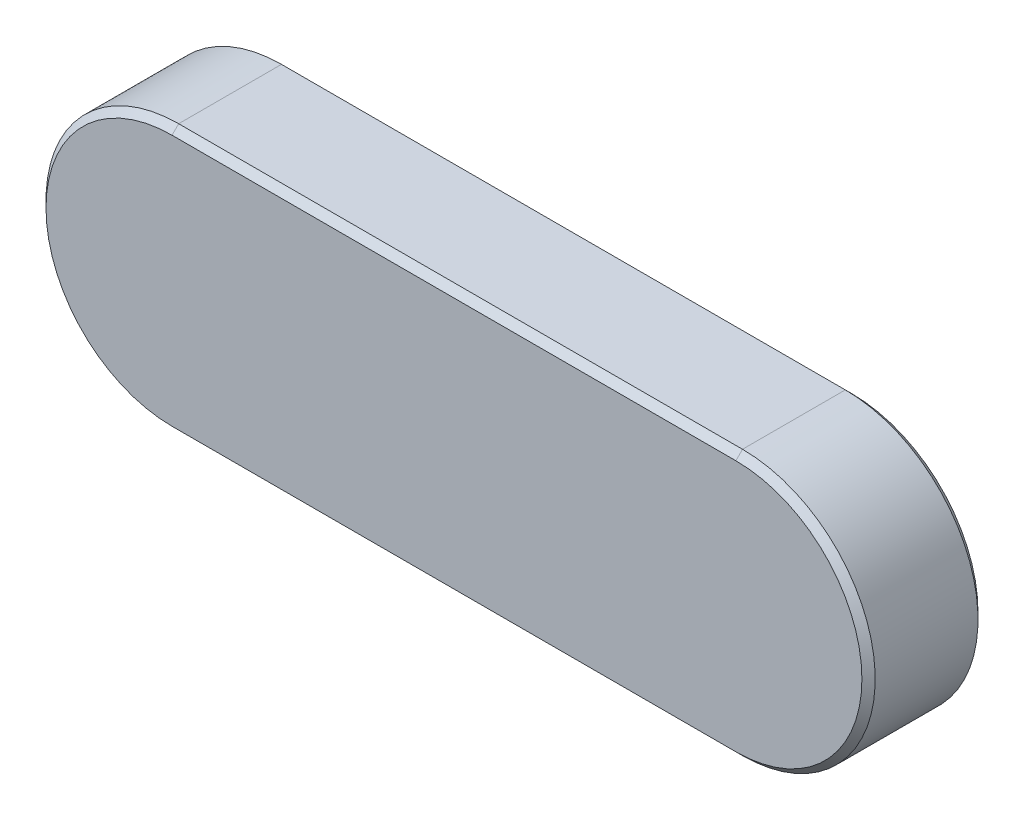
SolidWorks part; units mm, degrees
ref_plane "Front" through (0, 0, 0) normal (0, 0, 1) x (1, 0, 0)
ref_plane "Top" through (0, 0, 0) normal (0, 1, 0) x (1, 0, 0)
ref_plane "Right" through (0, 0, 0) normal (1, 0, 0) x (0, 0, -1)
sketch "Sketch1" plane through (0, 0, 0) normal (0, 0, 1) x (1, 0, 0)
  line L0 (-52.9374, 0) -> (56.5693, 0) construction
  line L1 (0, 11.4129) -> (0, -11.6476) construction
  line L3 (-17, 8) -> (17, 8)
  line L5 (-17, -8) -> (17, -8)
  arc A0 (17, 8) -> (17, -8) centre (17, 0) cw
  arc A1 (-17, 8) -> (-17, -8) centre (-17, 0) ccw
extrude "BaseKey" add sketch "Sketch1" along normal mid plane 7
sketch "Sketch2" plane through (0, 0, 0) normal (0, 0, 1) x (1, 0, 0)
  line L0 (-25, 8) -> (25, 8)
  line L1 (25, 8) -> (25, -8)
  line L2 (25, 0) -> (0, 0) construction
  line L3 (0, 0) -> (0, 8) construction
  line L4 (-25, -8) -> (25, -8)
  line L5 (-25, 8) -> (-25, -8)
  line L6 (-17, 8) -> (17, 8) construction
  point P8 (0, -8)
  dimension "D1" = 50
  dimension "D2" = 16
extrude "Extrude1" [suppressed] add sketch "Sketch2" along normal mid plane 7
sketch "Sketch3" plane through (0, 0, 0) normal (0, 0, 1) x (1, 0, 0)
  line L0 (-17, -8) -> (25, -8)
  line L1 (-17, 8) -> (25, 8)
  line L2 (25, 8) -> (25, -8)
  line L3 (-25, 0) -> (25, 0) construction
  arc A0 (17, -8) -> (17, 8) centre (17, 0) ccw construction
  arc A1 (-17, 8) -> (-17, -8) centre (-17, 0) ccw
  dimension "D1" = 16
  dimension "D2" = 50
extrude "Extrude2" [suppressed] add sketch "Sketch3" along normal mid plane 7
chamfer "Chamfer1" distance 0.4 angle 45 8 edges at (0, 8, 3.5) (0, 8, -3.5) (0, -8, -3.5) (0, -8, 3.5) (-25, 0, -3.5) (25, 0, -3.5) (-25, 0, 3.5) (25, 0, 3.5)
chamfer "Chamfer2" [suppressed] distance 0.4 angle 45
equation "\"D1@Sketch2\" = \"L@Sketch1\""
equation "\"D2@Sketch2\" = \"b@Sketch1\""
equation "\"D1@Extrude1\" = \"h@BaseKey\""
equation "\"D2@Sketch3\" = \"L@Sketch1\""
equation "\"D1@Sketch3\" = \"b@Sketch1\""
equation "\"D1@Extrude2\" = \"h@BaseKey\""
